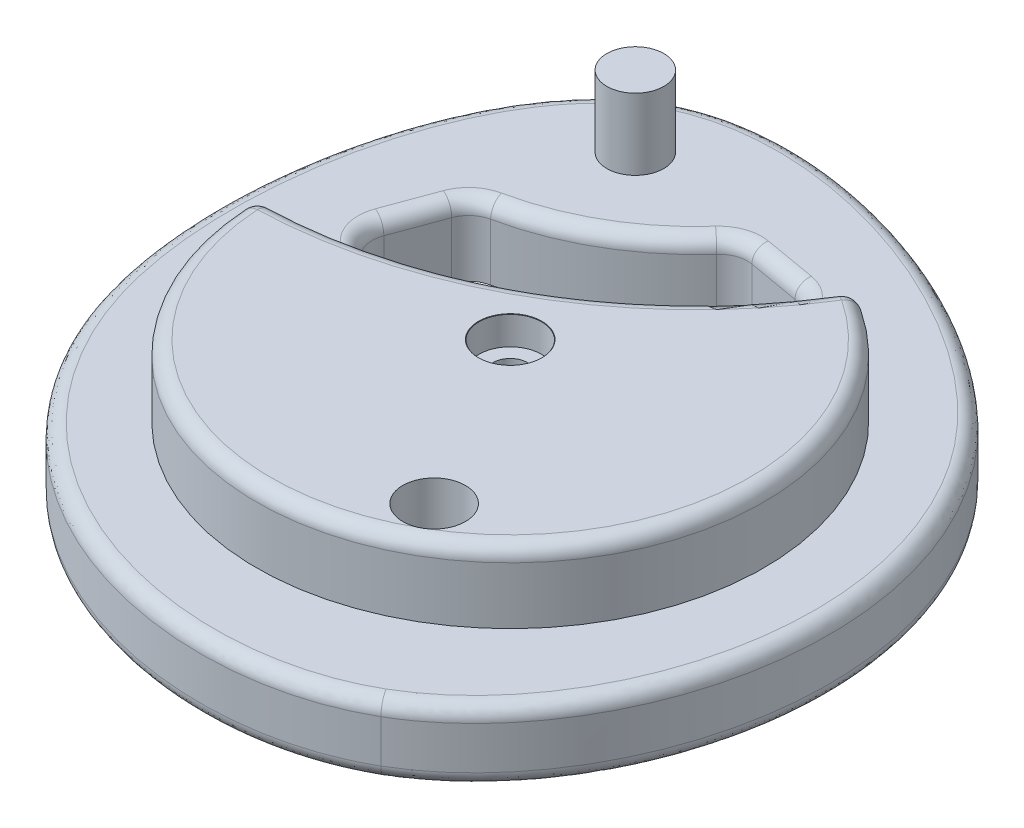
SolidWorks part; units mm, degrees
note: The reader was unsure of these and kept them because the rebuilt part matched: shared geometry of "Sketch1<3>", "Sketch2<4>".
ref_plane "Front Plane" through (0, 0, 0) normal (0, 0, 1) x (1, 0, 0)
ref_plane "Top Plane" through (0, 0, 0) normal (0, 1, 0) x (1, 0, 0)
ref_plane "Right Plane" through (0, 0, 0) normal (1, 0, 0) x (0, 0, -1)
sketch "Sketch1" plane through (0, 0, 0) normal (0, 1, 0) x (1, 0, 0)
  line L0 (0, 0) -> (48, 0)
  line L1 (48, 0) -> (36, 20.7846)
  line L2 (36, 20.7846) -> (0, 0)
  line L3 (48, 0) -> (30.2, 30.8305)
  line L4 (30.2, 30.8305) -> (30.2, 0)
  line L5 (36, 20.7846) -> (32.5, 26.8468) construction
  circle A0 centre (48, 0) radius 17.8
  arc A1 (30.2, 0) -> (56.9, 15.4153) centre (30.2, 30.8305) ccw
  circle A2 centre (36, 20.7846) radius 2
  circle A3 centre (48, 0) radius 31
  dimension "D4" = 17.8
  dimension "D6" = 4
  dimension "D1" = 48
  dimension "D2" = 41.5692
  dimension "D3" = 24
  dimension "D5" = 30.8305
  dimension "D7" = 7
extrude "Boss-Extrude1" add sketch "Sketch1" against normal blind 5 contours L0 A3 L3 A2 A0 | A1 L0 L1 | A0 A1 L3 | L3 A1 A0 | A1 L1 L0 A0 | A2 L2 L4 A0 L3 | L2 A3 L0 L4 | L4 A3 L2 | L3 A3 L4 L2 A2 | L1 A2 L3 | L3 A2 L2 | L2 A2 L1
extrude "Boss-Extrude2" add sketch "Sketch1<3>" along normal blind 5 contours L1 A2 L3 | L3 A2 L2 | L2 A2 L1 | A1 L1 L0 A0 | A1 L0 L1
sketch "Sketch1<3>" plane through (0, 0, 0) normal (0, 1, 0) x (1, 0, 0) same geometry as "Sketch1"
sketch "Sketch2" plane through (0, -5, 0) normal (0, -1, 0) x (1, 0, 0)
  line L0 (36, -20.7846) -> (63.5, 26.8468) construction
  line L1 (36, -20.7846) -> (33.5, -25.1147) construction
  line L2 (26.1894, -20.894) -> (39.599, -28.636) construction
  line L3 (30.2, -5) -> (32.9309, -12.4321)
  line L4 (52.5699, -17.9153) -> (44.7681, -19.2663)
  circle A0 centre (36, -20.7846) radius 2 construction
  arc A1 (56.9, -15.4153) -> (30.2, 0) centre (30.2, -30.8305) ccw construction
  arc A2 (56.9, -15.4153) -> (30.2, 0) centre (48, 0) ccw construction
  circle A3 centre (36, -20.7846) radius 2
  arc A4 (56.9, -15.4153) -> (30.2, 0) centre (30.2, -30.8305) ccw
  arc A5 (56.9, -15.4153) -> (30.2, 0) centre (48, 0) ccw
  circle A6 centre (48, 0) radius 31 construction
  circle A7 centre (48, 0) radius 31
  circle A8 centre (55.3, 12.644) radius 2.2
  arc A9 (52.5699, -17.9153) -> (30.2, -5) centre (30.2, -30.8305) ccw
  arc A10 (44.7681, -19.2663) -> (32.9309, -12.4321) centre (30.2, -30.8305) ccw
  spline S0 degree 3 poles (33.5, -25.1147) (25.4366, -20.4593) (21.4725, -0.9473) (33.9931, 23.52) (51.4997, 26.616) (60.4, 21.4774) knots 0 0 0 0 0.405972 0.488715 1 1 1 1
  spline S1 degree 3 poles (33.5, -25.1147) (41.5634, -29.7701) (60.4433, -23.4472) (75.3724, -0.3703) (69.3003, 16.3388) (60.4, 21.4774) knots 0 0 0 0 0.405972 0.488715 1 1 1 1
  point P2 (37, -19.0526)
  point P18 (56.4, 14.5492)
  point P19 (43.1153, -8.4606)
  point P22 (35, -22.5167)
  point P25 (56.9, 15.4153)
  point P26 (45.6153, -4.1305)
  point P28 (39.5, -14.7224)
  circle M8 centre (48, 0) radius 31
  dimension "D2" = 3
  dimension "D4" = 4.4
  dimension "D5" = 5
  dimension "D1" = 7
  dimension "D3" = 1
  dimension "D6" = 5
extrude "Cut-Extrude3" cut sketch "Sketch2" against normal through all contours S1 S0 M8 | A8
extrude "Cut-Extrude4" cut sketch "Sketch2<4>" against normal through all contours A10 L4 A9 L3
sketch "Sketch2<4>" plane through (0, -5, 0) normal (0, -1, 0) x (1, 0, 0) same geometry as "Sketch2"
fillet "Fillet1" radius 2 4 edges at (32.9309, -2.5, -12.4321) (44.7681, -2.5, -19.2663) (30.2, -2.5, -5) (52.5699, -2.5, -17.9153)
sketch "Sketch3" plane through (0, -5, 0) normal (0, -1, 0) x (1, 0, 0)
  line L1 (62.2172, 13.6832) -> (60.0586, 17.422)
  line L2 (60.0586, 17.422) -> (55.7414, 17.422)
  line L3 (55.7414, 17.422) -> (53.5828, 13.6832)
  line L4 (53.5828, 13.6832) -> (55.7414, 9.9444)
  line L5 (55.7414, 9.9444) -> (60.0586, 9.9444)
  line L6 (60.0586, 9.9444) -> (62.2172, 13.6832)
sketch "Sketch4" plane through (0, -5, 0) normal (0, -1, 0) x (1, 0, 0)
  arc A0 (56.9, -15.4153) -> (30.2, 0) centre (48, 0) ccw construction
  arc A1 (56.9, -15.4153) -> (30.2, 0) centre (48, 0) ccw
  circle A2 centre (48, 0) radius 4.5
  spline S1 degree 3 poles (2516.9422, 1645.9118) (-321.6348, 4.5808) (29.7855, -70.837) (118.511, 66.312) (-343.2956, 249.907) (892.1989, -2846.9438) knots -2.053569 -2.053569 -2.053569 -2.053569 0.405972 0.488715 3.88958 3.88958 3.88958 3.88958 only from (33.5, -25.1147) to (60.4, 21.4774)
  spline S2 degree 3 poles (33.5, -25.1147) (41.5634, -29.7701) (60.4433, -23.4472) (75.3724, -0.3703) (69.3003, 16.3388) (60.4, 21.4774) knots 0 0 0 0 0.405972 0.488715 1 1 1 1
  spline S4 degree 3 poles (-2839.6149, -692.3727) (460.0728, -213.9178) (70.1723, 94.2202) (-4.2394, -51.1927) (236.7843, -317.8226) (238.9304, 2961.1202) knots -2.889577 -2.889577 -2.889577 -2.889577 0.511285 0.594028 3.053568 3.053568 3.053568 3.053568 only from (60.4, 21.4774) to (33.5, -25.1147)
  spline S5 degree 3 poles (60.4, 21.4774) (51.4997, 26.616) (33.9931, 23.52) (21.4725, -0.9473) (25.4366, -20.4593) (33.5, -25.1147) knots 0 0 0 0 0.511285 0.594028 1 1 1 1
  dimension "D2" = 9
  dimension "D1" = 0
extrude "Cut-Extrude7" cut sketch "Sketch4" against normal blind 4 contours A2
fillet "Fillet2" radius 1 2 edges at (30.2, 2.5, 0) (56.9, 2.5, -15.4153)
fillet "Fillet4" radius 1 12 edges at (31.5658, 0, -5.9375) (31.8951, 0, -9.6133) (33.1055, 0, -12.1796) (39.5, 0, -14.7224) (44.8995, 0, -18.9888) (47.7271, 0, -18.7539) (51.0751, 0, -17.2012) (30.4903, 5, 0.3091) (57.0226, 5, -15.0093) (43.1153, 0, -8.4606) (56.9, 5, 15.4153) (45.6153, 5, -4.1305)
fillet "Fillet5" radius 1 2 edges
fillet "Fillet6" radius 1 2 edges
hole_wizard "CBORE for M2 SHCS1" positions "Sketch5" profile "Sketch7" counterbore size "M2" standard "ANSI Metric"
sketch "Sketch5" plane through (0, 5, 0) normal (0, 1, 0) x (1, 0, 0)
  point P0 (48, 0)
sketch "Sketch7" plane through (48, 5, 0) normal (1, 0, 0) x (0, 0, 1)
  line L0 (0, 0) -> (0, 15.721)
  line L1 (0, 15.721) -> (1.2, 15)
  line L2 (1.2, 15) -> (1.2, 2)
  line L3 (1.2, 2) -> (2.2, 2)
  line L5 (2.2, 2) -> (2.2, 0.025)
  line L6 (2.2, 0.025) -> (2.225, 0)
  line L7 (2.225, 0) -> (0, 0)
  line L8 (-2.2, 0.025) -> (-2.225, 0) construction
  line L10 (0, 15.721) -> (-1.2, 15) construction
  line L11 (0, -6.35) -> (0, 107.95) construction
  dimension "Hole Dia." = 2.4
  dimension "Hole Depth" = 15
  dimension "C'Bore Dia." = 4.4
  dimension "C'Bore Depth" = 2
  dimension "Near C'Sink Dia." = 4.45
  dimension "Near C'Sink Angle" = 90
  dimension "Drill Angle" = 118
sketch "Sketch8" plane through (0, -5, 0) normal (0, -1, 0) x (1, 0, 0)
  line L0 (48, 0) -> (55.3, 12.644) construction
  line L2 (48.384, 2.6651) -> (50.384, 6.1292)
  line L3 (48.384, 2.6651) -> (50.116, 1.6651)
  line L4 (50.116, 1.6651) -> (52.116, 5.1292)
  line L5 (50.384, 6.1292) -> (52.116, 5.1292)
  line L6 (48.384, 2.6651) -> (52.116, 5.1292) construction
  line L7 (50.116, 1.6651) -> (50.384, 6.1292) construction
  circle A0 centre (48, 0) radius 4.5 construction
  point P4 (50.25, 3.8971)
  dimension "D1" = 2
  dimension "D2" = 2
extrude "Cut-Extrude8" cut sketch "Sketch8" against normal up to surface (4 mm away) up to face at (48, -1, -1.2)
sketch "Sketch9" plane through (0, -5, 0) normal (0, -1, 0) x (1, 0, 0)
  line L1 (59.6263, 12.8249) -> (57.3065, 16.4812)
  line L2 (57.3065, 16.4812) -> (52.9801, 16.3002)
  line L3 (52.9801, 16.3002) -> (50.9737, 12.463)
  line L4 (50.9737, 12.463) -> (53.2935, 8.8068)
  line L5 (53.2935, 8.8068) -> (57.6199, 8.9877)
  line L6 (57.6199, 8.9877) -> (59.6263, 12.8249)
  circle A0 centre (55.3, 12.644) radius 3.75 construction
  dimension "D1" = 7.5
extrude "Cut-Extrude9" cut sketch "Sketch9" against normal blind 3
equation "\"DrivenWheelD\"= 80"
equation "\"DriverD\"= 35"
equation "\"PinD\"= 4"
equation "\"a\" = 24"
equation "\"b\" = sqr ( \"c\" ^ 2 - \"a\" ^ 2 )"
equation "\"c\" = \"a\" / sin ( 180 / \"n\" )"
equation "\"s\" = \"a\" + \"b\" - \"c\""
equation "\"w\"= ( \"p\" + \"t\" )"
equation "\"y\"= \"a\" - ( \"p\" * 1.5 )"
equation "\"z\" = \"y\" - \"t\""
equation "\"p\"= 4"
equation "\"n\" = 6"
equation "\"t\"= 0.2"
equation "\"v\" = \"b\" * \"z\" / \"a\""
equation "\"D1@Sketch1\"=\"c\""
equation "\"D2@Sketch1\"=\"b\""
equation "\"D3@Sketch1\"=\"a\""
equation "\"D4@Sketch1\"=\"z\""
equation "\"D5@Sketch1\"=\"v\""
equation "\"D6@Sketch1\"=\"p\""
equation "\"D7@Sketch1\"=\"p\"+3"
